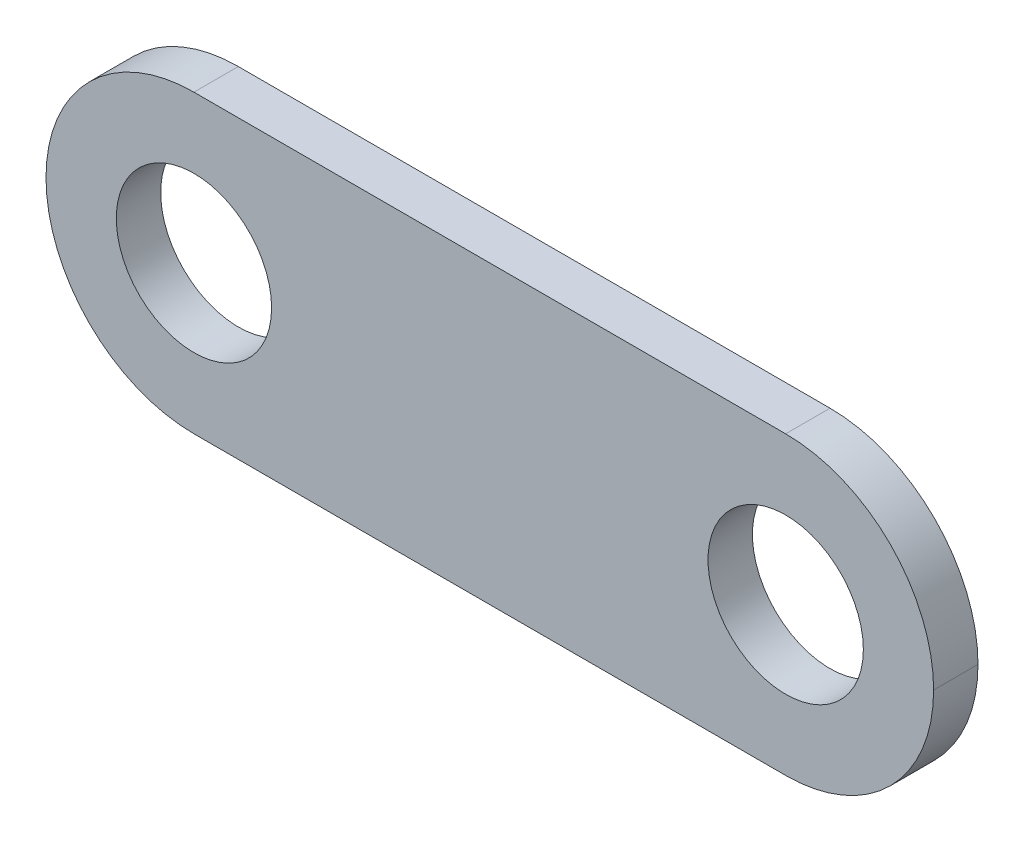
SolidWorks part; units mm, degrees
ref_plane "正面" through (0, 0, 0) normal (0, 0, 1) x (1, 0, 0)
ref_plane "平面" through (0, 0, 0) normal (0, 1, 0) x (1, 0, 0)
ref_plane "右側面" through (0, 0, 0) normal (1, 0, 0) x (0, 0, -1)
sketch "ｽｹｯﾁ1" plane through (0, 0, 0) normal (0, 0, 1) x (1, 0, 0)
  line L1 (0, 0) -> (60, 0)
  line L2 (0, 0) -> (0, 20)
  line L3 (0, 20) -> (60, 20)
  line L4 (60, 0) -> (60, 20)
  dimension "D1" = 60
  dimension "D2" = 20
extrude "ﾎﾞｽ - 押し出し1" add sketch "ｽｹｯﾁ1" along normal blind 3
fillet "ﾌｨﾚｯﾄ1" radius 10 4 edges at (60, 0, 1.5) (60, 20, 1.5) (0, 0, 1.5) (0, 20, 1.5)
hole_wizard "M10 すきま穴1" positions "ｽｹｯﾁ2" profile "ｽｹｯﾁ3" hole size "M10" standard "JIS" end condition through all
sketch "ｽｹｯﾁ2" plane through (0, 0, 3) normal (0, 0, 1) x (1, 0, 0)
  line L0 (50, 20) -> (10, 20) construction
  point P0 (10, 10)
  point P2 (50, 10)
  dimension "D1" = 10
  dimension "D2" = 40
  dimension "D3" = 10
  dimension "D4" = 10
sketch "ｽｹｯﾁ3" plane through (10, 10, 3) normal (1, 0, 0) x (0, -1, 0)
  line L0 (0, 0) -> (0, 3)
  line L1 (0, 3) -> (5.25, 3)
  line L2 (5.25, 3) -> (5.25, 0)
  line L5 (5.25, 0) -> (0, 0)
  line L11 (0, -6.35) -> (0, 107.95) construction
  dimension "通し穴の直径" = 10.5
  dimension "通し穴の深さ" = 3
